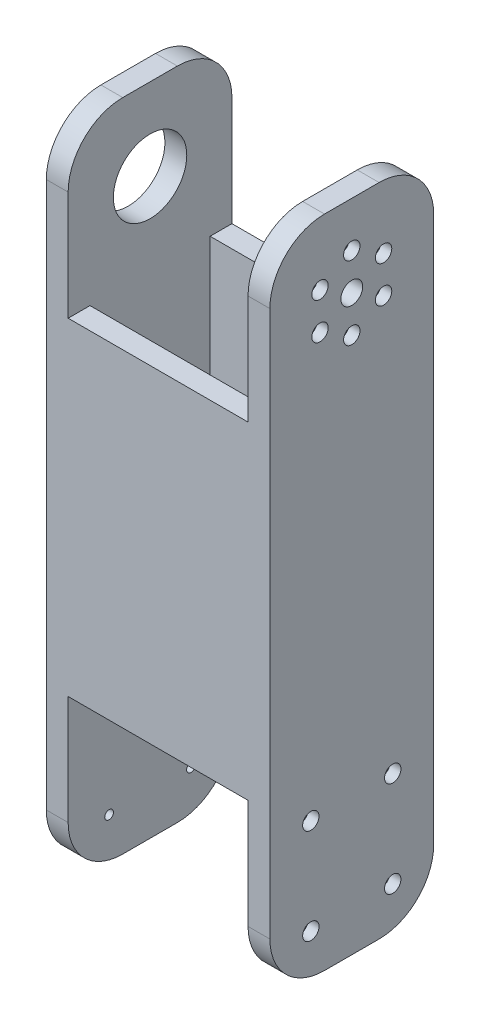
SolidWorks part; units mm, degrees
ref_plane "前视基准面" through (0, 0, 0) normal (0, 0, 1) x (1, 0, 0)
ref_plane "上视基准面" through (0, 0, 0) normal (0, 1, 0) x (1, 0, 0)
ref_plane "右视基准面" through (0, 0, 0) normal (1, 0, 0) x (0, 0, -1)
other "Configuration Table"
sketch "草图1" plane through (0, 0, 0) normal (1, 0, 0) x (0, 0, -1)
  line L1 (30, -120) -> (-30, -120)
  line L2 (30, -120) -> (30, 120)
  line L3 (30, 120) -> (-30, 120)
  line L4 (-30, -120) -> (-30, 120)
  line L5 (30, -120) -> (-30, 120) construction
  line L6 (30, 120) -> (-30, -120) construction
  point P0 (0, 0)
  dimension "D1" = 240
  dimension "D2" = 60
extrude "凸台-拉伸1" add sketch "草图1" along normal blind 8
sketch "草图2" plane through (8, 0, 0) normal (1, 0, 0) x (0, 0, -1)
  line L1 (30, 120) -> (-30, 120) construction
  circle A12 centre (0, 90) radius 13.45
  point P6 (0, 120)
  point P26 (0, 90)
  dimension "D11" = 26.9
  dimension "D2" = 30
extrude "切除-拉伸1" cut sketch "草图2" against normal through all
sketch "草图3" plane through (8, 0, 0) normal (1, 0, 0) x (0, 0, -1)
  line L0 (-30, 120) -> (-30, -120) construction
  line L1 (-22, -60) -> (-30, -60)
  line L2 (-22, -60) -> (-22, 60)
  line L3 (-22, 60) -> (-30, 60)
  line L4 (-30, -60) -> (-30, 60)
  line L5 (-22, -60) -> (-30, 60) construction
  line L6 (-22, 60) -> (-30, -60) construction
  line L7 (30, -60) -> (22, -60)
  line L8 (30, -60) -> (30, 60)
  line L9 (30, 60) -> (22, 60)
  line L10 (22, -60) -> (22, 60)
  line L11 (30, -60) -> (22, 60) construction
  line L12 (30, 60) -> (22, -60) construction
  line L13 (30, -120) -> (30, 120) construction
  line L14 (30, 120) -> (-30, 120) construction
  line L15 (-30, -120) -> (30, -120) construction
  point P0 (-26, 0)
  point P5 (26, 0)
  dimension "D1" = 60
  dimension "D2" = 60
  dimension "D3" = 60
  dimension "D4" = 60
  dimension "D5" = 8
  dimension "D6" = 8
extrude "凸台-拉伸2" add sketch "草图3" along normal blind 65.9
sketch "草图4" plane through (73.9, 0, 0) normal (1, 0, 0) x (0, 0, -1)
  line L0 (30, -120) -> (-30, 120) construction
  line L1 (30, -120) -> (-30, -120)
  line L2 (30, -120) -> (30, 120)
  line L3 (30, 120) -> (-30, 120)
  line L4 (-30, -120) -> (-30, 120)
  line L5 (30, -120) -> (-30, 120) construction
  line L6 (30, 120) -> (-30, -120) construction
  line L7 (30, 120) -> (-30, 120) construction
  point P0 (0, 0)
extrude "凸台-拉伸3" add sketch "草图4" along normal blind 8
fillet "圆角1" radius 20 8 edges at (4, -120, 30) (4, -120, -30) (4, 120, -30) (4, 120, 30) (77.9, 120, -30) (77.9, 120, 30) (77.9, -120, -30) (77.9, -120, 30)
sketch "草图9" plane through (73.9, 0, 0) normal (-1, 0, 0) x (0, 0, 1)
  circle A0 centre (0, 90) radius 19 construction
  circle A2 centre (0, 109) radius 1.6
  circle A3 centre (19, 90) radius 1.6
  circle A4 centre (0, 71) radius 1.6
  circle A5 centre (-19, 90) radius 1.6
  point P14 (0, 90)
  dimension "D1" = 38
  dimension "D2" = 3.2
sketch "草图10" plane through (81.9, 0, 0) normal (1, 0, 0) x (0, 0, -1)
  circle A0 centre (0, 90) radius 4
  circle A1 centre (0, 90) radius 13.5 construction
  circle A2 centre (0, 103.5) radius 1.6
  circle A3 centre (11.6913, 96.75) radius 1.6
  circle A4 centre (11.6913, 83.25) radius 1.6
  circle A5 centre (0, 76.5) radius 1.6
  circle A6 centre (-11.6913, 83.25) radius 1.6
  circle A7 centre (-11.6913, 96.75) radius 1.6
  point P18 (0, 90)
  dimension "D1" = 8
  dimension "D2" = 27
  dimension "D3" = 3.2
  dimension "D4" = 6
extrude "切除-拉伸2" cut sketch "草图10" against normal up to next
sketch "草图11" plane through (81.9, 0, 0) normal (1, 0, 0) x (0, 0, -1)
  line L1 (15, -105) -> (-15, -105) construction
  line L2 (15, -105) -> (15, -70) construction
  line L3 (15, -70) -> (-15, -70) construction
  line L4 (-15, -105) -> (-15, -70) construction
  line L5 (15, -105) -> (-15, -70) construction
  line L6 (15, -70) -> (-15, -105) construction
  line L7 (-30, 100) -> (-30, -100) construction
  line L8 (30, -100) -> (30, 100) construction
  line L9 (0, -70) -> (0, -105) construction
  line L10 (-15, -87.5) -> (15, -87.5) construction
  line L11 (-22, -60) -> (-30, -60) construction
  circle A0 centre (-15, -70) radius 1.6
  circle A1 centre (15, -70) radius 1.6
  circle A2 centre (15, -105) radius 1.6
  circle A3 centre (-15, -105) radius 1.6
  point P0 (0, -87.5)
  dimension "D5" = 3.2
  dimension "D1" = 10
  dimension "D2" = 15
  dimension "D3" = 15
  dimension "D4" = 35
extrude "切除-拉伸3" cut sketch "草图11" against normal through all
sketch "草图12" plane through (81.9, 0, 0) normal (1, 0, 0) x (0, 0, -1)
  circle A0 centre (0, 103.45) radius 3
  circle A1 centre (0, 90) radius 13.45 construction
  circle A2 centre (11.648, 96.725) radius 3
  circle A3 centre (11.648, 83.275) radius 3
  circle A4 centre (0, 76.55) radius 3
  circle A5 centre (-11.648, 83.275) radius 3
  circle A6 centre (-11.648, 96.725) radius 3
  point P4 (0, 90)
  point P16 (0, 90)
  dimension "D1" = 6
  dimension "D2" = 6
extrude "切除-拉伸4" cut sketch "草图12" against normal blind 4
sketch "草图13" plane through (81.9, 0, 0) normal (1, 0, 0) x (0, 0, -1)
  line L2 (0, -70) -> (0, -105) construction
  line L3 (-15, -87.5) -> (15, -87.5) construction
  circle A0 centre (-15, -70) radius 3
  circle A1 centre (15, -70) radius 3
  circle A2 centre (15, -105) radius 3
  circle A3 centre (-15, -105) radius 3
  dimension "D1" = 6
extrude "切除-拉伸5" cut sketch "草图13" against normal blind 4
sketch "草图14" plane through (0, 0, 0) normal (-1, 0, 0) x (0, 0, 1)
  line L0 (0, -70) -> (0, -105) construction
  line L1 (-15, -87.5) -> (15, -87.5) construction
  circle A0 centre (-15, -70) radius 3
  circle A1 centre (15, -70) radius 3
  circle A2 centre (15, -105) radius 3
  circle A3 centre (-15, -105) radius 3
  dimension "D1" = 6
extrude "切除-拉伸6" cut sketch "草图14" against normal blind 4
